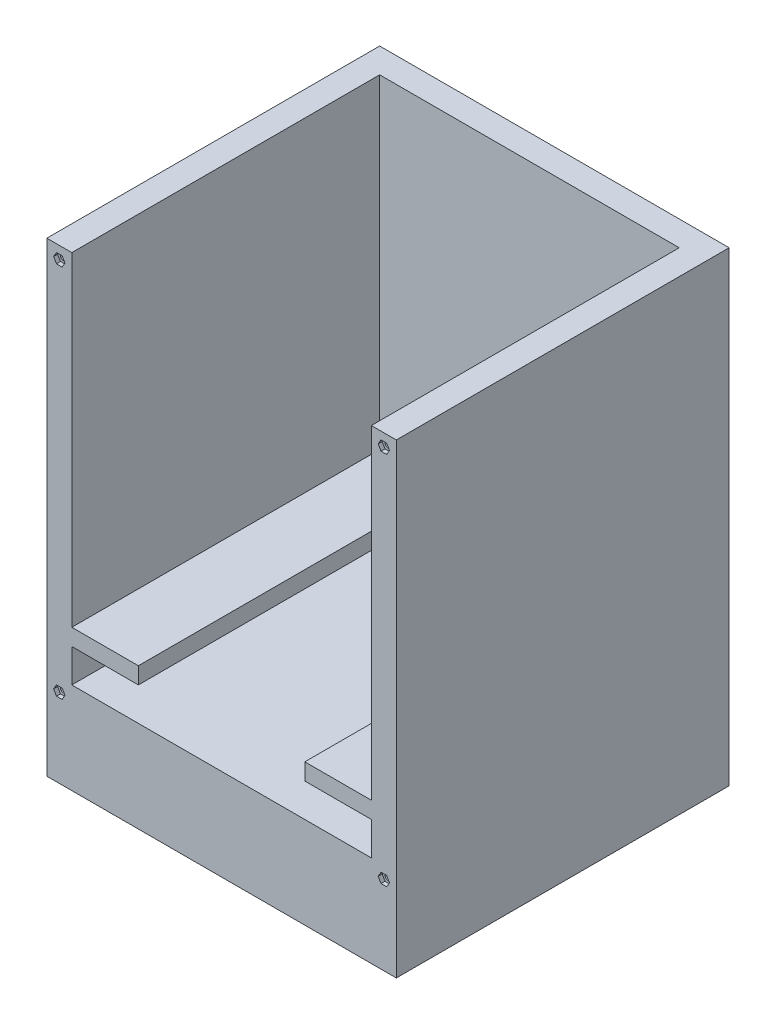
SolidWorks part; units mm, degrees
ref_plane "Front Plane" through (0, 0, 0) normal (0, 0, 1) x (1, 0, 0)
ref_plane "Top Plane" through (0, 0, 0) normal (0, 1, 0) x (1, 0, 0)
ref_plane "Right Plane" through (0, 0, 0) normal (1, 0, 0) x (0, 0, -1)
sketch "Sketch2" plane through (0, 0, 0) normal (0, 1, 0) x (1, 0, 0)
  line L0 (-90, 0) -> (90, 0)
  line L1 (90, 0) -> (90, -185)
  line L2 (-90, 0) -> (-90, -185)
  line L3 (-90, -185) -> (-105, -185)
  line L4 (-105, -185) -> (-105, 15)
  line L5 (-105, 15) -> (105, 15)
  line L6 (105, 15) -> (105, -185)
  line L7 (105, -185) -> (90, -185)
  dimension "D1" = 180
  dimension "D2" = 185
  dimension "D3" = 15
  dimension "D4" = 15
extrude "Boss-Extrude1" add sketch "Sketch2" along normal blind 225
ref_plane "Plane1" through (0, 30, 0) normal (0, 1, 0) x (1, 0, 0)
sketch "Sketch3" plane through (0, 30, 0) normal (0, 1, 0) x (1, 0, 0)
  line L0 (-90, -185) -> (-50, -185)
  line L1 (-50, -185) -> (-50, -10)
  line L2 (-50, -10) -> (50, -10)
  line L3 (50, -10) -> (50, -185)
  line L4 (50, -185) -> (90, -185)
  line L5 (-90, 0) -> (90, 0) construction
  line L14 (-90, -185) -> (-90, 0)
  line L15 (-90, 0) -> (90, 0)
  line L16 (90, 0) -> (90, -185)
  line L17 (90, -185) -> (105, -185)
  line L18 (105, -185) -> (105, 15)
  line L19 (105, 15) -> (-105, 15)
  line L20 (-105, 15) -> (-105, -185)
  line L21 (-105, -185) -> (-90, -185)
  line L22 (-90, -185) -> (-90, 0)
  line L23 (-90, 0) -> (90, 0)
  line L24 (90, 0) -> (90, -185)
  dimension "D1" = 40
  dimension "D2" = 10
  dimension "D3" = 0
extrude "Boss-Extrude2" add sketch "Sketch3" against normal blind 10
sketch "Sketch6" plane through (0, 0, 0) normal (0, -1, 0) x (1, 0, 0)
  line L1 (-105, 185) -> (105, 185)
  line L2 (-105, 185) -> (-105, -15)
  line L3 (-105, -15) -> (105, -15)
  line L4 (105, 185) -> (105, -15)
extrude "Boss-Extrude3" add sketch "Sketch6" along normal blind 15
sketch "Sketch7" plane through (0, 0, -15) normal (0, 0, -1) x (-1, 0, 0)
  line L0 (-105, 225) -> (-105, -15) construction
  line L1 (-90, 20) -> (-47.75, 20)
  line L2 (-90, 20) -> (-90, 0)
  line L3 (-90, 0) -> (-47.75, 0)
  line L4 (-47.75, 20) -> (-47.75, 0)
  line L5 (105, -15) -> (-105, -15) construction
  line L7 (0, -1000) -> (0, 49000) construction
  line L8 (90, 0) -> (47.75, 0)
  line L9 (47.75, 20) -> (47.75, 0)
  line L10 (90, 20) -> (47.75, 20)
  line L11 (90, 20) -> (90, 0)
  dimension "D1" = 15
  dimension "D2" = 15
  dimension "D3" = 42.25
  dimension "D4" = 20
extrude "Cut-Extrude2" cut sketch "Sketch7" against normal up to surface (15 mm away) contours L4 L1 L2 L3 region at (68.875, 10, -15) up to face at (0, 10, 0)
sketch "Sketch5" plane through (0, 0, 185) normal (0, 0, 1) x (1, 0, 0)
  line L0 (-105, 225) -> (-90, 225) construction
  line L1 (-105, 225) -> (-105, -15) construction
  line L2 (0, 0) -> (0, 50000) construction
  line L4 (105, -15) -> (-105, -15) construction
  circle A0 centre (-97.5, 217.5) radius 1.65
  circle A1 centre (97.5, 217.5) radius 1.65
  circle A2 centre (-97.5, -7.5) radius 1.65
  circle A3 centre (97.5, -7.5) radius 1.65
  point P4 (-97.5, 225)
  dimension "D1" = 3.3
  dimension "D4" = 3.3
  dimension "D2" = 7.5
  dimension "D3" = 7.5
  dimension "D5" = 7.5
  dimension "D6" = 7.5
extrude "Cut-Extrude1" cut sketch "Sketch5" against normal blind 10 contours A2 | A1 | A0 | A3
sketch "Sketch8" plane through (0, 0, 185) normal (0, 0, 1) x (1, 0, 0)
  line L0 (0, -1000) -> (0, 49000) construction
  line L1 (-95.7968, 220.45) -> (-99.2032, 220.45)
  line L2 (-99.2032, 220.45) -> (-100.9064, 217.5)
  line L3 (-100.9064, 217.5) -> (-99.2032, 214.55)
  line L4 (-99.2032, 214.55) -> (-95.7968, 214.55)
  line L5 (-95.7968, 214.55) -> (-94.0936, 217.5)
  line L6 (-94.0936, 217.5) -> (-95.7968, 220.45)
  line L7 (94.0936, 217.5) -> (95.7968, 220.45)
  line L8 (95.7968, 214.55) -> (94.0936, 217.5)
  line L9 (99.2032, 214.55) -> (95.7968, 214.55)
  line L10 (100.9064, 217.5) -> (99.2032, 214.55)
  line L11 (99.2032, 220.45) -> (100.9064, 217.5)
  line L12 (95.7968, 220.45) -> (99.2032, 220.45)
  line L13 (94.0936, -7.5) -> (95.7968, -4.55)
  line L14 (-95.7968, -4.55) -> (-99.2032, -4.55)
  line L15 (-99.2032, -4.55) -> (-100.9064, -7.5)
  line L16 (-100.9064, -7.5) -> (-99.2032, -10.45)
  line L17 (-99.2032, -10.45) -> (-95.7968, -10.45)
  line L18 (-95.7968, -10.45) -> (-94.0936, -7.5)
  line L19 (-94.0936, -7.5) -> (-95.7968, -4.55)
  line L20 (95.7968, -10.45) -> (94.0936, -7.5)
  line L21 (99.2032, -10.45) -> (95.7968, -10.45)
  line L22 (100.9064, -7.5) -> (99.2032, -10.45)
  line L23 (99.2032, -4.55) -> (100.9064, -7.5)
  line L24 (95.7968, -4.55) -> (99.2032, -4.55)
  circle A0 centre (-97.5, 217.5) radius 2.95 construction
  circle A1 centre (-97.5, -7.5) radius 2.95 construction
  circle M7 centre (-97.5, 217.5) radius 1.65
  circle M8 centre (-97.5, -7.5) radius 1.65
  circle M26 centre (97.5, -7.5) radius 1.65
  dimension "D1" = 5.9
  dimension "D2" = 5.9
extrude "Cut-Extrude3" cut sketch "Sketch8" along direction (0, 0, 1) on the side against the normal offset from surface (2.4 mm away) 2.4 contours L5 L6 L1 L2 L3 L4 M7 | L18 L19 L14 L15 L16 L17 M8 | L24 L13 L20 L21 L22 L23 M26 | L10 L9 L8 L7 L12 L11 region at (-95.0233, 218.9299, 185) region at (95.0233, -6.0701, 185) region at (-95.0233, -6.0701, 185) up to face at (-95.85, 217.5, 185)
sketch "Sketch10" plane through (0, -15, 0) normal (0, -1, 0) x (1, 0, 0)
  line L0 (105, -15) -> (105, 185) construction
  line L1 (-95, -5) -> (95, -5)
  line L2 (-95, -5) -> (-95, 175)
  line L3 (-95, 175) -> (95, 175)
  line L4 (95, -5) -> (95, 175)
  line L5 (-95, -5) -> (95, 175) construction
  line L6 (-95, 175) -> (95, -5) construction
  line L8 (105, 185) -> (-105, 185) construction
  line L9 (-105, 185) -> (-105, -15) construction
  line L10 (-105, -15) -> (105, -15) construction
  point P0 (0, 85)
  line M5 (-105, 185) -> (-105, -15)
  line M6 (-105, -15) -> (105, -15)
  line M7 (105, -15) -> (105, 185)
  line M8 (105, 185) -> (-105, 185)
  dimension "D1" = 10
  dimension "D2" = 10
  dimension "D3" = 10
  dimension "D4" = 10
extrude "Boss-Extrude4" add sketch "Sketch10" along normal blind 40 contours L4 L1 L2 L3 M8 M5 M6 M7 region at (0, -15, 182.1)
sketch "Sketch11" plane through (0, 0, 0) normal (0, 1, 0) x (1, 0, 0)
  circle A0 centre (0, -85) radius 5
  dimension "D1" = 10
extrude "Boss-Extrude5" add sketch "Sketch11" along normal blind 5 draft 5
